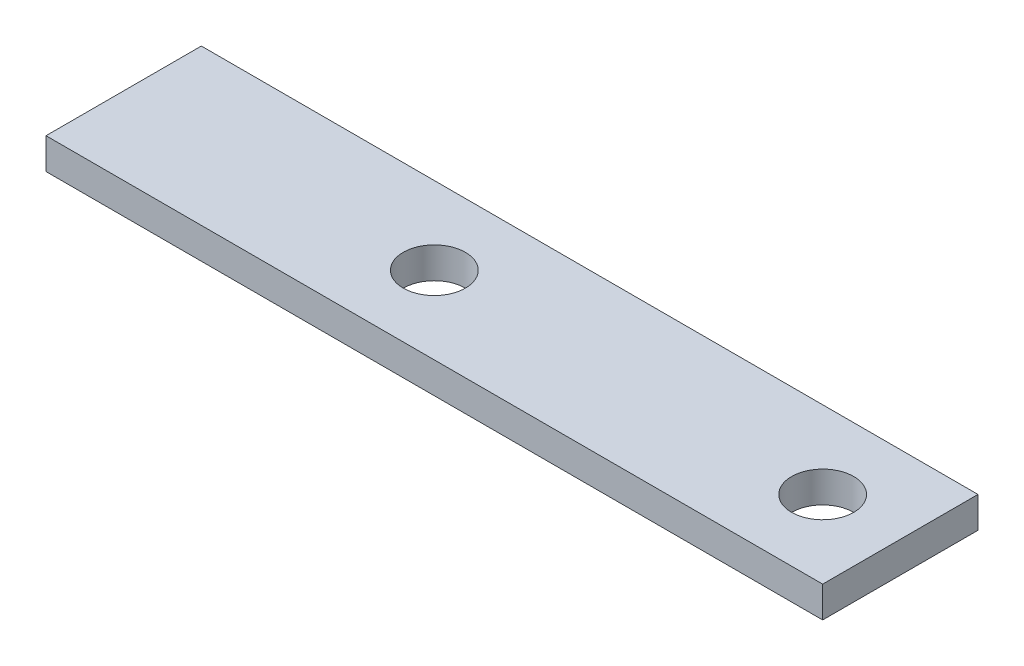
SolidWorks part; units mm, degrees
ref_plane "Спереди" through (0, 0, 0) normal (0, 0, 1) x (1, 0, 0)
ref_plane "Сверху" through (0, 0, 0) normal (0, 1, 0) x (1, 0, 0)
ref_plane "Справа" through (0, 0, 0) normal (1, 0, 0) x (0, 0, -1)
sketch "Эскиз1" plane through (0, 0, 0) normal (1, 0, 0) x (0, 0, -1)
  line L0 (0, 0) -> (20, 0)
extrude "Вытянуть-Тонкостенный1" add sketch "Эскиз1" along normal blind 100 thin thin type one direction wall 4
sketch "Эскиз2" plane through (0, 0, 0) normal (0, 1, 0) x (1, 0, 0)
  circle A0 centre (90, 10) radius 4
  circle A1 centre (40, 10) radius 4
  dimension "D1" = 2
extrude "Вырез-Вытянуть1" cut sketch "Эскиз2" against normal through all
